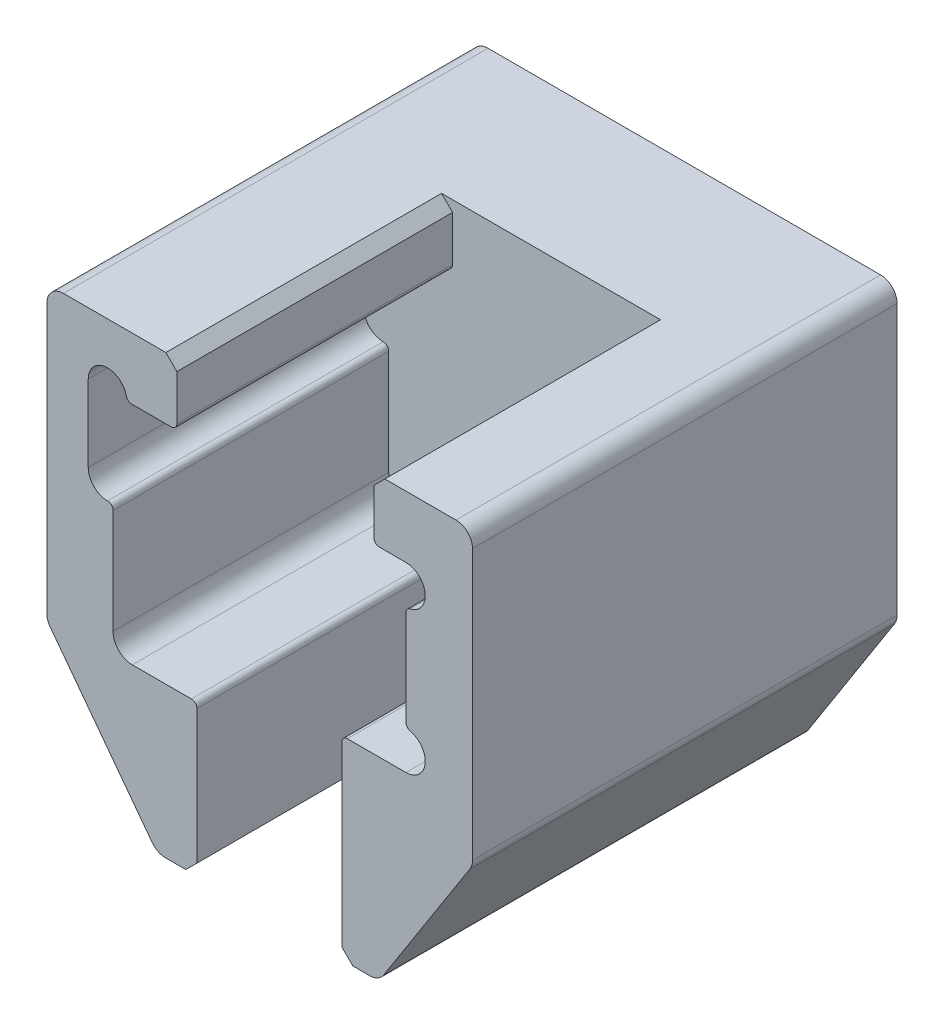
SolidWorks part; units mm, degrees
ref_plane "Alzado" through (0, 0, 0) normal (0, 0, 1) x (1, 0, 0)
ref_plane "Planta" through (0, 0, 0) normal (0, 1, 0) x (1, 0, 0)
ref_plane "Vista lateral" through (0, 0, 0) normal (1, 0, 0) x (0, 0, -1)
sketch "Croquis1" plane through (0, 0, 0) normal (0, 0, 1) x (1, 0, 0)
  line L0 (0, 13.3) -> (0, 39.7)
  line L1 (54.8768, 0) -> (0, 0) construction
  line L2 (0, 0) -> (0, 49.5322) construction
  line L3 (0, 39.7) -> (38.6, 39.7)
  line L4 (38.6, 39.7) -> (38.6, 13.3)
  line L5 (38.6, 13.3) -> (30.1, 0)
  line L6 (30.1, 0) -> (10, 0)
  line L7 (10, 0) -> (0, 13.3)
  dimension "D1" = 38.6
  dimension "D2" = 39.7
  dimension "D3" = 26.4
  dimension "D4" = 8.5
  dimension "D5" = 26.4
  dimension "D6" = 10
extrude "Saliente-Extruir1" add sketch "Croquis1" along normal blind 38.5
sketch "Croquis2" plane through (0, 0, 38.5) normal (0, 0, 1) x (1, 0, 0)
  line L1 (29.65, 39.7) -> (29.65, 34.1)
  line L2 (29.65, 34.1) -> (32.56, 34.1)
  line L3 (32.56, 30.6) -> (32.56, 21.1)
  line L4 (32.56, 17.6) -> (26.74, 17.6)
  line L5 (26.74, 17.6) -> (26.74, 0)
  line L6 (10, 0) -> (30.1, 0) construction
  line L7 (26.74, 0) -> (13.6, 0)
  line L8 (13.6, 0) -> (13.6, 13.65)
  line L9 (13.6, 13.65) -> (7.75, 13.65)
  line L10 (6, 15.4) -> (6, 25.4)
  line L15 (6, 25.4) -> (5.5, 25.4)
  line L17 (7.25, 34.1) -> (11.79, 34.1)
  line L18 (11.79, 34.1) -> (11.79, 39.7)
  line L19 (38.6, 39.7) -> (0, 39.7) construction
  line L20 (0, 39.7) -> (0, 13.3) construction
  line L24 (11.79, 39.7) -> (29.65, 39.7)
  line L26 (3.75, 34.1) -> (3.75, 27.15)
  arc A1 (3.75, 27.15) -> (5.5, 25.4) centre (5.5, 27.15) ccw
  arc A3 (32.56, 17.6) -> (32.56, 21.1) centre (32.56, 19.35) ccw
  arc A4 (32.56, 30.6) -> (32.56, 34.1) centre (32.56, 32.35) ccw
  arc A9 (7.25, 34.1) -> (3.75, 34.1) centre (5.5, 34.1) ccw
  arc A10 (7.75, 13.65) -> (6, 15.4) centre (7.75, 15.4) cw
  dimension "D19" = 3.5
  dimension "D20" = 3.5
  dimension "D21" = 3.5
  dimension "D23" = 17.6
  dimension "D8" = 3.5
  dimension "D10" = 1.75
  dimension "D3" = 16.5
  dimension "D4" = 5.6
  dimension "D5" = 8.7
  dimension "D6" = 13.65
  dimension "D7" = 3.75
  dimension "D9" = 11.79
  dimension "D11" = 26.56
  dimension "D13" = 6
  dimension "D14" = 13.6
  dimension "13.14" = 13.14
  dimension "D17" = 17.86
extrude "Cortar-Extruir1" cut sketch "Croquis2" against normal blind 25
fillet "Redondeo2" radius 0.5 8 edges at (13.6, 13.65, 26) (11.79, 34.1, 26) (29.65, 34.1, 26) (32.56, 30.6, 26) (32.56, 21.1, 26) (26.74, 17.6, 26) (7.25, 34.1, 26) (6, 25.4, 26)
fillet "Redondeo3" radius 1.5 6 edges at (38.6, 13.3, 19.25) (0, 13.3, 19.25) (10, 0, 19.25) (30.1, 0, 19.25) (38.6, 39.7, 19.25) (0, 39.7, 19.25)
sketch "Croquis4" plane through (0, 0, 0) normal (0, 0, -1) x (-1, 0, 0)
  line L0 (-10.7489, 0) -> (-29.2785, 0) construction
  line L1 (-38.6, 13.7384) -> (-38.6, 38.2) construction
  point P0 (-20.6, 10)
  dimension "D1" = 10
  dimension "D2" = 18
hole_wizard "Perforador para roscar Helicoil de M81" positions "Croquis5" profile "Croquis6" hole size "M8x1.0" standard "Ansi Metric"
sketch "Croquis5" plane through (0, 0, 0) normal (0, 0, -1) x (-1, 0, 0)
  point P0 (-20.6, 10)
sketch "Croquis6" plane through (20.6, 10, 0) normal (1, 0, 0) x (0, 1, 0)
  line L0 (0, 0) -> (0, 11.9786)
  line L1 (0, 11.9786) -> (4.125, 9.5)
  line L2 (4.125, 9.5) -> (4.125, 0)
  line L5 (4.125, 0) -> (0, 0)
  line L10 (0, 11.9786) -> (-4.125, 9.5) construction
  line L11 (0, -6.35) -> (0, 107.95) construction
  dimension "Diámetro de taladro" = 8.25
  dimension "Profundidad de taladro" = 9.5
  dimension "Ángulo de perforador" = 118
chamfer "Chaflán1" distance 1 angle 45 4 edges at (11.79, 39.7, 26) (29.65, 39.7, 26) (13.6, 0, 26) (26.74, 0, 26)
